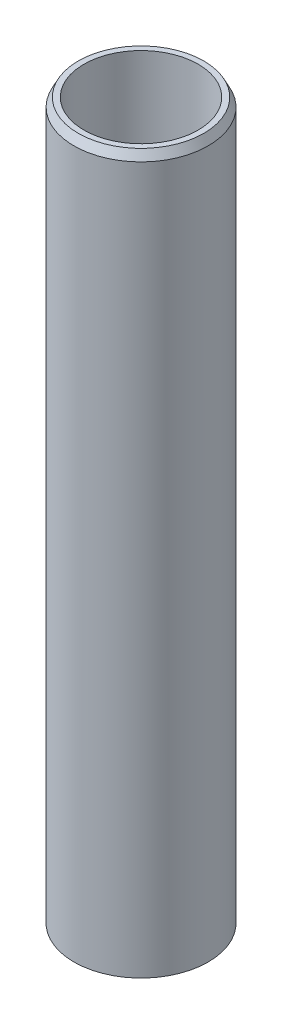
SolidWorks part; units mm, degrees
ref_plane "Front Plane" through (0, 0, 0) normal (0, 0, 1) x (1, 0, 0)
ref_plane "Top Plane" through (0, 0, 0) normal (0, 1, 0) x (1, 0, 0)
ref_plane "Right Plane" through (0, 0, 0) normal (1, 0, 0) x (0, 0, -1)
sketch "Sketch1" plane through (0, 0, 0) normal (0, 1, 0) x (1, 0, 0)
  circle A0 centre (0, 0) radius 45
  dimension "SHAFT_OD" = 90
extrude "Boss-Extrude1" add sketch "Sketch1" along normal blind 482.2674
sketch "Sketch2" plane through (0, 0, 0) normal (0, 1, 0) x (1, 0, 0)
  circle A0 centre (0, 0) radius 38.2644
  dimension "BORE_D" = 76.5288
extrude "Cut-Extrude1" cut sketch "Sketch2" along normal through all
chamfer "Chamfer1" distance 5.7749 angle 27.119 2 edges at (0, 482.2674, 45) (0, 0, 45) first distance on face at (0, 482.2674, 45) first distance on face at (0, 0, 38.2644)
